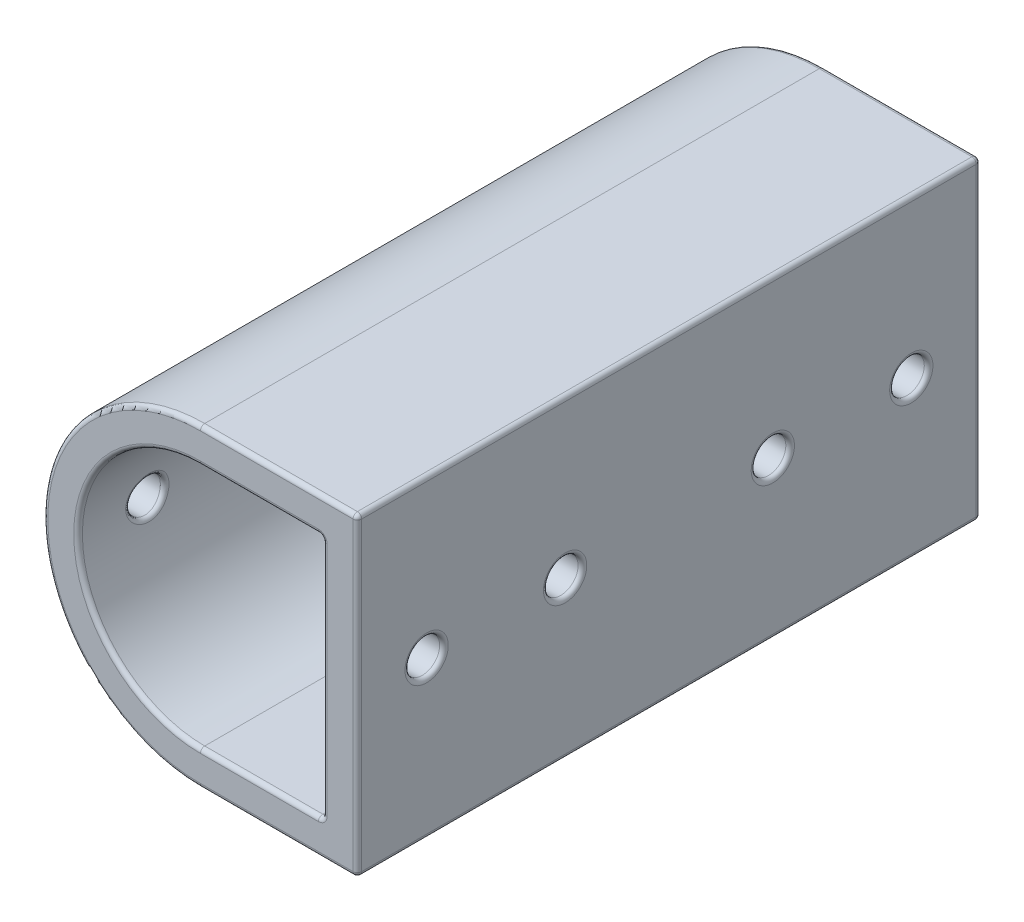
SolidWorks part; units mm, degrees
ref_plane "Front Plane" through (0, 0, 0) normal (0, 0, 1) x (1, 0, 0)
ref_plane "Top Plane" through (0, 0, 0) normal (0, 1, 0) x (1, 0, 0)
ref_plane "Right Plane" through (0, 0, 0) normal (1, 0, 0) x (0, 0, -1)
sketch "Sketch2" plane through (0, 0, 0) normal (0, 0, 1) x (1, 0, 0)
  line L1 (0, 13.9792) -> (14.3954, 13.9792)
  line L2 (0, 13.9792) -> (0, -14.8117)
  line L3 (0, -14.8117) -> (14.3955, -14.8117)
  line L4 (14.3954, 13.9792) -> (14.3955, -14.8117)
  line L5 (11.2204, -11.6367) -> (0, -11.6367)
  line L6 (11.2204, -11.6367) -> (11.2204, 10.8042)
  line L7 (11.2204, 10.8042) -> (0, 10.8042)
  arc A0 (0, -11.6367) -> (0, 10.8042) centre (0, -0.4163) cw
  arc A1 (0, 13.9792) -> (0, -14.8117) centre (0, -0.4163) ccw
  dimension "D1" = 28.7909
  dimension "D2" = 14.3954
  dimension "D3" = 3.175
  dimension "D4" = 3.175
  dimension "D5" = 3.175
extrude "Boss-Extrude2" add sketch "Sketch2" along normal blind 57.15 contours L1 L4 L3 A1
extrude "Cut-Extrude1" cut sketch "Sketch2<10>" against normal blind 57.15 and the other way blind 57.15 contours L7 A0 L5 L6
sketch "Sketch2<10>" plane through (0, 0, 0) normal (0, 0, 1) x (1, 0, 0) same geometry as "Sketch2"
sketch "Sketch3" plane through (14.3954, 0, 0) normal (1, 0, 0) x (0, 0, -1)
  line L0 (-57.15, 13.9792) -> (0, 13.9792) construction
  line L1 (0, 13.9792) -> (0, -14.8117) construction
  line L2 (0, -14.8117) -> (-57.15, -14.8117) construction
  line L3 (-57.15, -14.8117) -> (-57.15, 13.9792) construction
  line L4 (-57.15, -0.4163) -> (0, -0.4163) construction
  line L5 (-28.575, 13.9792) -> (-28.575, -14.8117) construction
  circle A0 centre (-50.8, -0.4163) radius 1.5875
  circle A1 centre (-38.1, -0.4163) radius 1.5875
  circle A4 centre (-19.05, -0.4163) radius 1.5875
  circle A5 centre (-6.35, -0.4163) radius 1.5875
  dimension "D3" = 3.175
  dimension "D1" = 6.35
  dimension "D2" = 12.7
extrude "Cut-Extrude2" cut sketch "Sketch3" against normal blind 38.1
fillet "Fillet2" radius 0.3969 36 edges at (7.1977, 13.9792, 57.15) (7.1977, -14.8117, 57.15) (7.1977, 13.9792, 0) (7.1977, -14.8117, 0) (5.6102, -11.6367, 0) (5.6102, -11.6367, 57.15) (11.2204, -0.4163, 57.15) (11.2204, -11.6367, 28.575) (11.2204, -0.4163, 0) (11.2204, -0.4163, 7.9375) (11.2204, -0.4163, 20.6375) (11.2204, -0.4163, 39.6875) (11.2204, -0.4163, 52.3875) (14.3955, -14.8117, 28.575) (14.3954, -0.4163, 57.15) (14.3954, 13.9792, 28.575) (14.3954, -0.4163, 0) (14.3954, -2.0038, 6.35) (14.3954, -2.0038, 19.05) (14.3954, 1.1712, 38.1) (14.3954, 1.1712, 50.8) (5.6102, 10.8042, 57.15) (11.2204, 10.8042, 28.575) (5.6102, 10.8042, 0) (-11.2204, -0.4163, 0) (-11.2204, -0.4163, 57.15) (-11.113, -1.9653, 6.6974) (-11.113, -1.9653, 19.3974) (-11.113, -1.9653, 38.4474) (-11.113, -1.9653, 51.1474) (-14.3954, -0.4163, 57.15) (-14.3954, -0.4163, 0) (-14.312, -1.9637, 5.9957) (-14.312, -1.9637, 18.6957) (-14.312, -1.9637, 37.7457) (-14.312, -1.9637, 50.4457)
